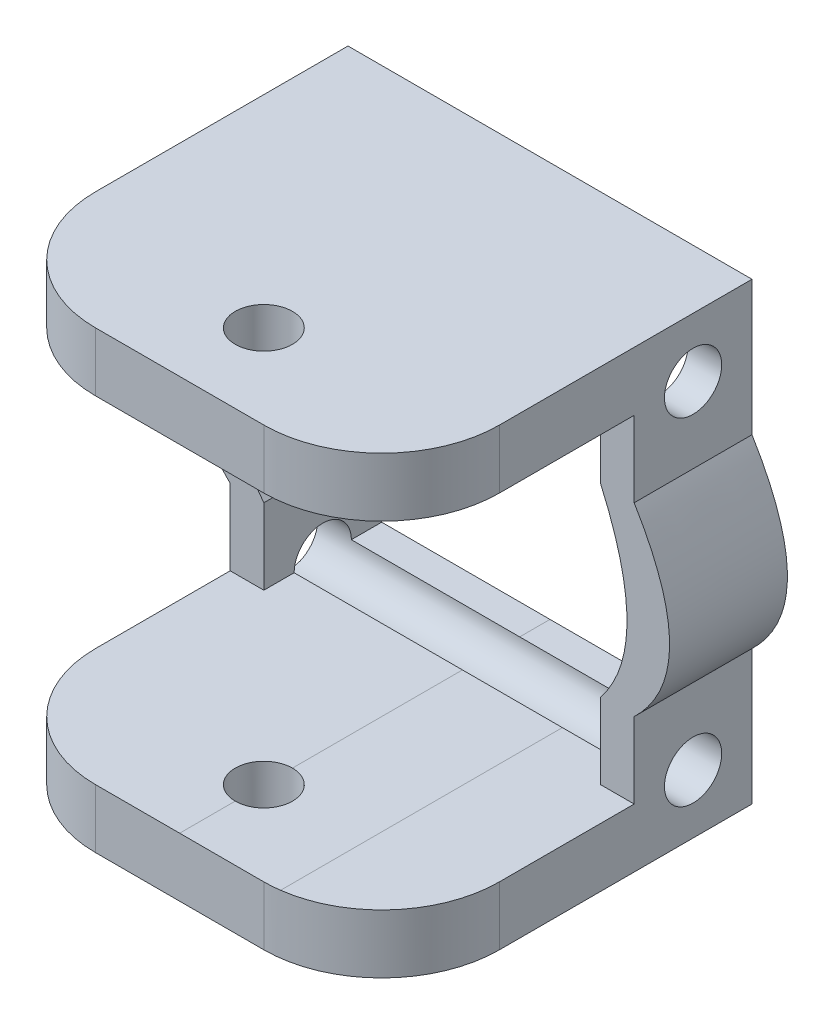
SolidWorks part; units mm, degrees
material "PLA"
ref_plane "Front Plane" through (0, 0, 0) normal (0, 0, 1) x (1, 0, 0)
ref_plane "Top Plane" through (0, 0, 0) normal (0, 1, 0) x (1, 0, 0)
ref_plane "Right Plane" through (0, 0, 0) normal (1, 0, 0) x (0, 0, -1)
sketch "Sketch1" plane through (0, 0, 0) normal (0, 0, 1) x (1, 0, 0)
  line L0 (-12, 13.5) -> (-12, 10)
  line L1 (-12, 10) -> (12, 10)
  line L2 (12, 10) -> (12, 13.5)
  line L3 (12, 13.5) -> (-12, 13.5)
  line L4 (-12, -10) -> (-12, -13.5)
  line L5 (-12, -13.5) -> (12, -13.5)
  line L6 (12, -13.5) -> (12, -10)
  line L7 (12, -10) -> (-12, -10)
  line L8 (0, 10.0333) -> (0, -15.702) construction
  line L9 (-12, 10) -> (-12, -10) construction
  line L10 (12, 10) -> (12, -10) construction
  line L11 (12, 10) -> (12, 5.5)
  line L12 (12, -10) -> (12, -5.5)
  line L13 (10, 10) -> (10, 5.5)
  line L14 (10, -10) -> (10, -5.5)
  line L17 (-10, -10) -> (-10, -5.5)
  line L18 (0, 0) -> (14.9553, 0) construction
  line L19 (-12, -10) -> (-12, -5.5)
  line L20 (-12, 10) -> (-12, 5.5)
  line L21 (-10, 10) -> (-10, 5.5)
  spline S0 degree 2 poles (12, 5.5) (16.2082, -1.4527) (12, -5.5) knots 0 0 0 0.703674 0.703674 0.703674
  spline S1 degree 2 poles (5.9341, -10) (5.4786, -10.0093) (0, -10) knots 0.968743 0.968743 0.968743 1 1 1
  spline S2 degree 2 poles (10, 5.5) (13.145, -1.5935) (10, -5.5) knots 0 0 0 0.703674 0.703674 0.703674
  spline S3 degree 2 poles (-12, 5.5) (-16.2082, -1.4527) (-12, -5.5) knots 0 0 0 0.703674 0.703674 0.703674
  spline S4 degree 2 poles (-10, 5.5) (-13.145, -1.5935) (-10, -5.5) knots 0 0 0 0.703674 0.703674 0.703674
  point P9 (0, -10)
  point P21 (12, 7.75)
  dimension "D6" = 8
  dimension "D5" = 8
  dimension "D1" = 3.5
  dimension "D2" = 3.5
  dimension "D3" = 24
  dimension "D4" = 27
  dimension "D7" = 2
extrude "Boss-Extrude1" add sketch "Sketch1" along normal blind 7 contours L2 L3 L0 L1 | S4 L21 L1 L20 S3 L19 L7 L17 | L13 S2 L14 L7 L12 S0 L11 L1 | L7 S1 L4 L5 L6 region at (0, 11.75, 0) region at (-11.7448, -0.0184, 0) region at (11.7448, -0.0184, 0) region at (-0.0008, -11.7504, 0)
extrude "Boss-Extrude2" add sketch "Sketch1<3>" along normal blind 15 from surface contours L2 L3 L0 L1 | L6 L7 L4 L5 region at (0, 11.75, 0) region at (-0.0008, -11.7504, 0) starting at face at (0.8901, -0.9, 7)
sketch "Sketch1<3>" plane through (0, 0, 0) normal (0, 0, 1) x (1, 0, 0) same geometry as "Sketch1"
fillet "Fillet1" radius 7 4 edges at (12, -11.75, 22) (-12, -11.75, 22) (12, 11.75, 22) (-12, 11.75, 22)
sketch "Sketch2" plane through (-12, 0, 0) normal (-1, 0, 0) x (0, 0, 1)
  line L0 (15, -13.5) -> (0, -13.5) construction
  line L3 (3.5, 10) -> (3.5, -10) construction
  line L4 (7, -10) -> (7, -5.5) construction
  line L5 (0, -13.5) -> (0, -5.5) construction
  point P0 (3.5, 10)
  point P1 (3.5, -10)
  dimension "D1" = 20
  dimension "D2" = 3.5
hole_wizard "M3 Clearance Hole1" positions "Sketch3" profile "Sketch4" hole size "M3" standard "ISO" end condition through all
sketch "Sketch3" plane through (-12, 0, 0) normal (-1, 0, 0) x (0, 0, 1)
  point P0 (3.5, 10)
  point P3 (3.5, -10)
sketch "Sketch4" plane through (-12, 10, 3.5) normal (0, 1, 0) x (0, 0, 1)
  line L0 (0, 0) -> (0, 26.1041)
  line L1 (0, 26.1041) -> (1.7, 26.1041)
  line L2 (1.7, 26.1041) -> (1.7, 0)
  line L5 (1.7, 0) -> (0, 0)
  line L11 (0, -6.35) -> (0, 107.95) construction
  dimension "Thru Hole Dia." = 3.4
  dimension "Thru Hole Depth" = 26.1041
sketch "Sketch5" plane through (0, 13.5, 0) normal (0, 1, 0) x (1, 0, 0)
  line L0 (12, 0) -> (-12, 0) construction
  point P0 (0, -17)
  dimension "D1" = 17
hole_wizard "M3 Clearance Hole2" positions "Sketch6" profile "Sketch7" hole size "M3" standard "ISO" end condition through all
sketch "Sketch6" plane through (0, 13.5, 0) normal (0, 1, 0) x (1, 0, 0)
  point P0 (0, -17)
sketch "Sketch7" plane through (0, 13.5, 17) normal (1, 0, 0) x (0, 0, 1)
  line L0 (0, 0) -> (0, 27)
  line L1 (0, 27) -> (1.7, 27)
  line L2 (1.7, 27) -> (1.7, 0)
  line L5 (1.7, 0) -> (0, 0)
  line L11 (0, -6.35) -> (0, 107.95) construction
  dimension "Thru Hole Dia." = 3.4
  dimension "Thru Hole Depth" = 27
